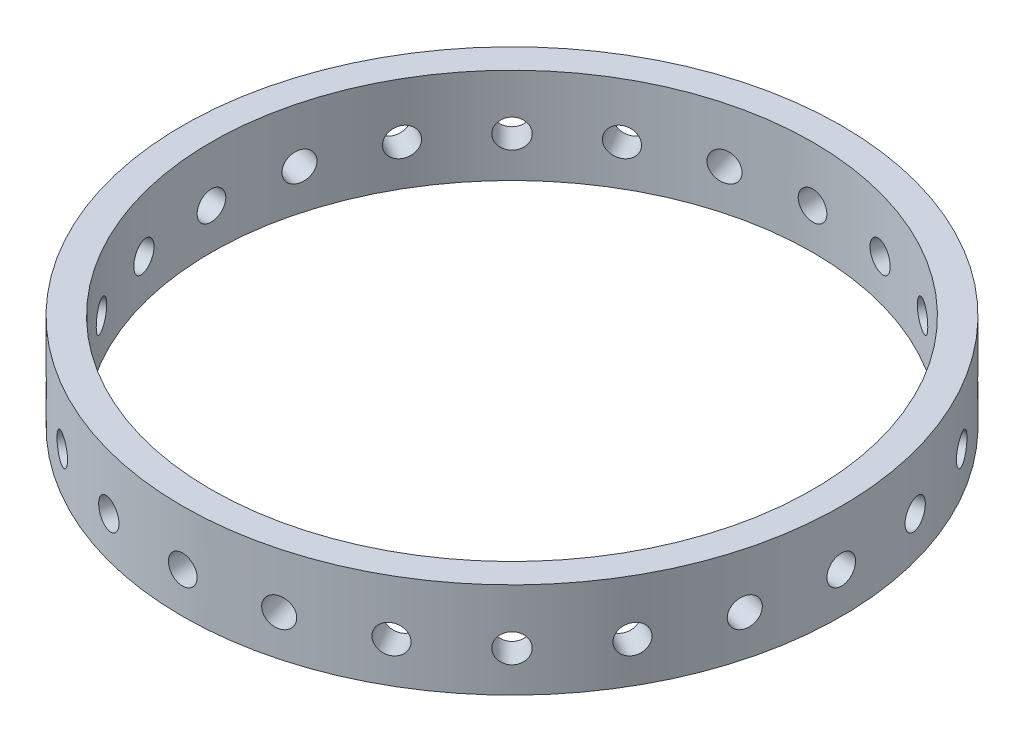
SolidWorks part; units mm, degrees
ref_plane "Front Plane" through (0, 0, 0) normal (0, 0, 1) x (1, 0, 0)
ref_plane "Top Plane" through (0, 0, 0) normal (0, 1, 0) x (1, 0, 0)
ref_plane "Right Plane" through (0, 0, 0) normal (1, 0, 0) x (0, 0, -1)
sketch "Sketch1" plane through (0, 0, 0) normal (0, 1, 0) x (1, 0, 0)
  circle A0 centre (0, 0) radius 69
  circle A1 centre (0, 0) radius 63
extrude "Boss-Extrude1" add sketch "Sketch1" along normal blind 20 contours A0 | A1
sketch "Sketch4" plane through (0, 0, 0) normal (0, 1, 0) x (1, 0, 0)
  line L0 (0, 0) -> (0, 69) construction
  circle A0 centre (0, 0) radius 69 construction
sketch "Sketch5" plane through (0, 0, 0) normal (0, 0, 1) x (1, 0, 0)
  line L0 (0, 0) -> (0, 8.5) construction
  circle A0 centre (0, 8.5) radius 3
extrude "Cut-Extrude1" cut sketch "Sketch5" against normal blind 84
ref_axis "Axis2" through (0, 21, 0) along (0, -1, 0)
pattern_circular "CirPattern1" count 24 over 360 about axis through (0, 21, 0) along (0, -1, 0) of "Cut-Extrude1"
